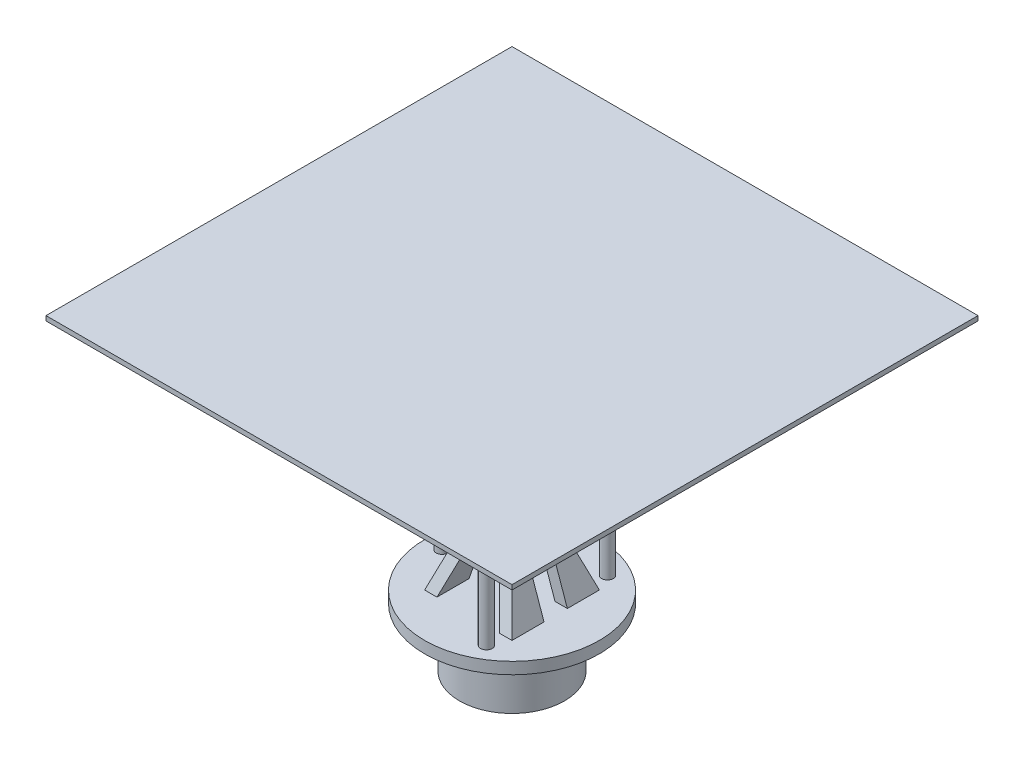
SolidWorks part; units mm, degrees
ref_plane "Front Plane" through (0, 0, 0) normal (0, 0, 1) x (1, 0, 0)
ref_plane "Top Plane" through (0, 0, 0) normal (0, 1, 0) x (1, 0, 0)
ref_plane "Right Plane" through (0, 0, 0) normal (1, 0, 0) x (0, 0, -1)
sketch "Sketch1" plane through (0, 0, 0) normal (0, 1, 0) x (1, 0, 0)
  circle A0 centre (0, 0) radius 75
extrude "Boss-Extrude1" add sketch "Sketch1" along normal blind 10
sketch "Sketch2" plane through (0, 0, 0) normal (0, -1, 0) x (1, 0, 0)
  circle A0 centre (0, 0) radius 45
  circle A1 centre (0, 0) radius 40
  dimension "D1" = 90
  dimension "D2" = 5
extrude "Boss-Extrude2" add sketch "Sketch2" along normal blind 50
sketch "Sketch5" plane through (0, 10, 0) normal (0, 1, 0) x (1, 0, 0)
  line L1 (37.5, -37.5) -> (-37.5, -37.5)
  line L2 (37.5, -37.5) -> (37.5, 37.5)
  line L3 (37.5, 37.5) -> (-37.5, 37.5)
  line L4 (-37.5, -37.5) -> (-37.5, 37.5)
  line L5 (37.5, -37.5) -> (-37.5, 37.5) construction
  line L6 (37.5, 37.5) -> (-37.5, -37.5) construction
  point P0 (0, 0)
  dimension "D1" = 75
  dimension "D2" = 75
extrude "Boss-Extrude3" add sketch "Sketch5" along normal blind 50
sketch "Sketch6" plane through (0, 0, 37.5) normal (0, 0, 1) x (1, 0, 0)
  line L0 (20, 60) -> (37.5, 10)
  line L1 (0, 10) -> (0, 60) construction
  line L2 (-37.5, 60) -> (37.5, 60) construction
  line L3 (20, 60) -> (-20, 60)
  line L4 (-20, 60) -> (-37.5, 10)
  line L5 (-37.5, 10) -> (-42.6786, 10)
  line L6 (75, 10) -> (-75, 10) construction
  line L7 (-42.6786, 10) -> (-42.6786, 63.0346)
  line L8 (-42.6786, 63.0346) -> (43.0697, 63.0346)
  line L9 (43.0697, 63.0346) -> (43.0697, 10)
  line L10 (43.0697, 10) -> (37.5, 10)
  line L11 (-12.9052, 50) -> (-26.9052, 10)
  line L12 (12.9052, 50) -> (26.9052, 10)
  line L13 (12.9052, 50) -> (-12.9052, 50)
  line L14 (-37.5, 10) -> (37.5, 10) construction
  line L15 (10.5614, 56.6965) -> (28.0614, 6.6965) construction
  line L16 (-10.5614, 56.6965) -> (-28.0614, 6.6965) construction
  line L17 (20, 50) -> (-20, 50) construction
  line L18 (-26.9052, 10) -> (26.9052, 10)
extrude "Cut-Extrude2" cut sketch "Sketch6" against normal blind 103
sketch "Sketch7" plane through (0, 0, 0) normal (1, 0, 0) x (0, 0, -1)
  line L0 (-37.5, 10) -> (37.5, 10) construction
  line L1 (0, 10) -> (0, 60) construction
  line L2 (37.5, 60) -> (-37.5, 60) construction
  line L3 (20, 60) -> (-20, 60)
  line L4 (-20, 60) -> (-37.5, 10)
  line L5 (20, 60) -> (37.5, 10)
  line L6 (-37.5, 10) -> (-47.693, 10)
  line L7 (75, 10) -> (-75, 10) construction
  line L8 (-47.693, 10) -> (-47.693, 63.7646)
  line L9 (-47.693, 63.7646) -> (47.4497, 63.7646)
  line L10 (47.4497, 63.7646) -> (47.4497, 10)
  line L11 (47.4497, 10) -> (37.5, 10)
  dimension "D1" = 20
extrude "Cut-Extrude3" cut sketch "Sketch7" against normal blind 103 and the other way blind 103
sketch "Sketch9" plane through (0, 0, 0) normal (1, 0, 0) x (0, 0, -1)
  line L0 (-37.5, 10) -> (37.5, 10) construction
  line L3 (-10, 10) -> (-10, 60)
  line L4 (10, 10) -> (10, 60)
  line L5 (-10, 60) -> (10, 60)
  line L6 (-10, 10) -> (10, 10)
extrude "Cut-Extrude4" cut sketch "Sketch9" against normal blind 103 and the other way blind 103
sketch "Sketch10" plane through (0, 10, 0) normal (0, 1, 0) x (1, 0, 0)
  circle A0 centre (0, 0) radius 5
extrude "Cut-Extrude5" cut sketch "Sketch10" against normal blind 103
sketch "Sketch11" plane through (0, 10, 0) normal (0, 1, 0) x (1, 0, 0)
  line L0 (0, 0) -> (-60, 0) construction
  circle A0 centre (-60, 0) radius 5
  circle A2 centre (30, 51.9615) radius 5
  circle A3 centre (30, -51.9615) radius 5
  point P15 (0, 0)
  dimension "D2" = 3
  dimension "D1" = 60
ref_plane "Plane1" through (0, 210, 0) normal (0, 1, 0) x (1, 0, 0)
sketch "Sketch12" plane through (0, 210, 0) normal (0, 1, 0) x (1, 0, 0)
  circle A0 centre (30, -51.9615) radius 5 construction
  circle A1 centre (30, 51.9615) radius 5 construction
  circle A2 centre (-60, 0) radius 5 construction
  circle A3 centre (30, -51.9615) radius 5
  circle A4 centre (30, 51.9615) radius 5
  circle A5 centre (-60, 0) radius 5
sketch3d "3DSketch1"
  line L0 (-60, 10, 0) -> (-60, 210, 0)
sweep "Sweep1" add profiles "Sketch11" path "3DSketch1"
sketch "Sketch13" plane through (0, 210, 0) normal (0, 1, 0) x (1, 0, 0)
  line L1 (-200, -200) -> (200, -200)
  line L2 (-200, -200) -> (-200, 200)
  line L3 (-200, 200) -> (200, 200)
  line L4 (200, -200) -> (200, 200)
  line L5 (-200, -200) -> (200, 200) construction
  line L6 (-200, 200) -> (200, -200) construction
  point P0 (0, 0)
  dimension "D1" = 400
  dimension "D2" = 400
extrude "Boss-Extrude4" add sketch "Sketch13" along normal blind 4
sketch "Sketch16" plane through (0, 0, -10) normal (0, 0, 1) x (1, 0, 0)
  line L0 (0, 60) -> (0, 50) construction
  line L1 (20, 60) -> (-20, 60) construction
  line L2 (-12.9052, 50) -> (12.9052, 50) construction
  circle A0 centre (0, 55) radius 15
  dimension "D1" = 30
sketch "Sketch17" plane through (0, 0, 0) normal (1, 0, 0) x (0, 0, -1)
  line L1 (10, 70) -> (10, 40) construction
  line L2 (10, 55) -> (10, 70)
  line L3 (10, 70) -> (-10, 70) construction
  line L4 (-10, 70) -> (-10, 55)
  line L5 (-10, 70) -> (-5, 70)
  line L6 (10, 70) -> (5, 70)
  line L7 (-5, 70) -> (-3.2375, 60.0045)
  line L8 (5, 70) -> (3.2375, 60.0045)
  line L9 (-3.2375, 60.0045) -> (3.2375, 60.0045)
  line L10 (10, 55) -> (-10, 55)
  dimension "D1" = 5
  dimension "D2" = 5
  dimension "D3" = 10
  dimension "D4" = 10
revolve "Revolve2" add sketch "Sketch17" angle 360 about L10
